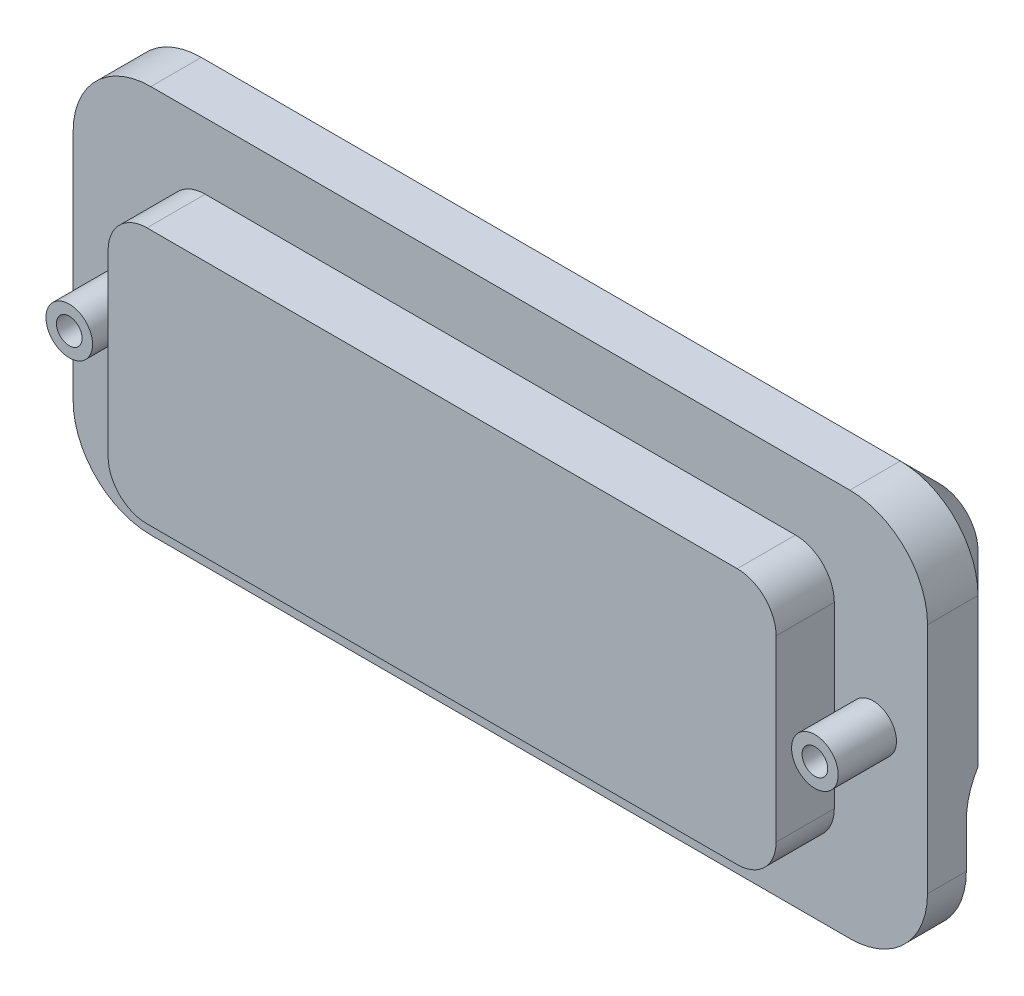
SolidWorks part; units mm, degrees
ref_plane "前视基准面" through (0, 0, 0) normal (0, 0, 1) x (1, 0, 0)
ref_plane "上视基准面" through (0, 0, 0) normal (0, 1, 0) x (1, 0, 0)
ref_plane "右视基准面" through (0, 0, 0) normal (1, 0, 0) x (0, 0, -1)
sketch "草图1" plane through (0, 0, 0) normal (0, 0, 1) x (1, 0, 0)
  line L1 (-55, 25) -> (55, 25)
  line L2 (-55, 25) -> (-55, -25)
  line L3 (-55, -25) -> (55, -25)
  line L4 (55, 25) -> (55, -25)
  line L5 (-55, 25) -> (55, -25) construction
  line L6 (-55, -25) -> (55, 25) construction
  point P0 (0, 0)
  dimension "D1" = 50
  dimension "D2" = 110
extrude "凸台-拉伸1" add sketch "草图1" along normal blind 5
sketch "草图2" plane through (0, 0, 5) normal (0, 0, 1) x (1, 0, 0)
  line L0 (-48, 0) -> (48, 0) construction
  line L1 (-38, 16.5) -> (38, 16.5)
  line L2 (-43, 11.5) -> (-43, -11.5)
  line L3 (-38, -16.5) -> (38, -16.5)
  line L4 (43, 11.5) -> (43, -11.5)
  line L5 (-43, 16.5) -> (43, -16.5) construction
  line L6 (-43, -16.5) -> (43, 16.5) construction
  circle A0 centre (-48, 0) radius 3
  circle A1 centre (48, 0) radius 3
  arc A2 (-38, 16.5) -> (-43, 11.5) centre (-38, 11.5) ccw
  arc A3 (38, 16.5) -> (43, 11.5) centre (38, 11.5) cw
  arc A4 (43, -11.5) -> (38, -16.5) centre (38, -11.5) cw
  arc A5 (-43, -11.5) -> (-38, -16.5) centre (-38, -11.5) ccw
  point P0 (0, 0)
  point P9 (0, 0)
  dimension "D4" = 6
  dimension "D5" = 6
  dimension "D6" = 5
  dimension "D7" = 5
  dimension "D1" = 86
  dimension "D2" = 33
  dimension "D3" = 96
extrude "凸台-拉伸2" add sketch "草图2" along normal blind 7.5
hole_wizard "M4 螺纹孔1" positions "草图5" profile "草图4" tap size "M4" standard "GB"
sketch "草图5" plane through (0, 0, 12.5) normal (0, 0, 1) x (1, 0, 0)
  point P1 (48, 0)
  point P4 (-48, 0)
sketch "草图4" plane through (48, 0, 12.5) normal (1, 0, 0) x (0, -1, 0)
  line L0 (0, 0) -> (0, 5.9914)
  line L1 (0, 5.9914) -> (1.65, 5)
  line L2 (1.65, 5) -> (1.65, 0)
  line L5 (1.65, 0) -> (0, 0)
  line L10 (0, 5.9914) -> (-1.65, 5) construction
  line L11 (0, -6.35) -> (0, 107.95) construction
  dimension "螺纹孔钻头直径" = 3.3
  dimension "螺纹孔钻头深度" = 5
  dimension "导头角度" = 118
cosmetic thread "孔螺蚊线1" parameters "D1"=5, "D2"=4
cosmetic thread "孔螺蚊线2" parameters "D1"=5, "D2"=4
sketch "草图6" plane through (0, 0, 0) normal (0, 0, -1) x (-1, 0, 0)
  line L0 (-55, -25) -> (-55, 25) construction
  line L1 (55, 25) -> (-55, 25)
  line L2 (55, 25) -> (55, 0)
  line L3 (55, 0) -> (-55, 0)
  line L4 (-55, 25) -> (-55, 0)
extrude "凸台-拉伸3" add sketch "草图6" along normal blind 6.5
fillet "圆角1" radius 10 4 edges at (55, 25, -0.75) (55, -25, 2.5) (-55, -25, 2.5) (-55, 25, -0.75)
chamfer "倒角1" distance 5 angle 45 5 edges at (-55, 7.5, -6.5) (55, 7.5, -6.5) (-52.0711, 22.0711, -6.5) (52.0711, 22.0711, -6.5) (0, 25, -6.5)
fillet "圆角2" radius 10 1 edges at (0, 0, 0)
